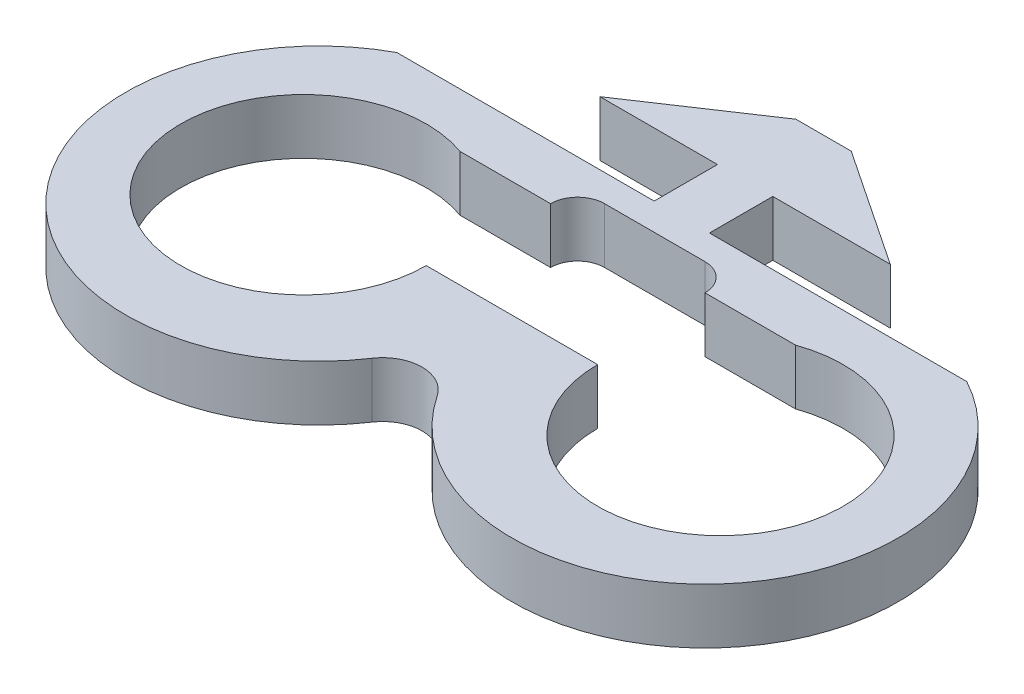
SolidWorks part; units mm, degrees
ref_plane "Front" through (0, 0, 0) normal (0, 0, 1) x (1, 0, 0)
ref_plane "Top" through (0, 0, 0) normal (0, 1, 0) x (1, 0, 0)
ref_plane "Right" through (0, 0, 0) normal (1, 0, 0) x (0, 0, -1)
sketch "Sketch1" plane through (0, 0, 0) normal (0, 1, 0) x (1, 0, 0)
  line L0 (-1.7907, 2.05) -> (-9.398, 2.05)
  line L2 (-1.7907, -2.05) -> (-1.7907, 2.05)
  line L4 (1.7907, -2.05) -> (1.7907, 2.05)
  line L7 (-9.398, 2.05) -> (-1.7907, 7.13)
  line L8 (-1.7907, 7.13) -> (1.7907, 7.13)
  line L9 (1.7907, 7.13) -> (9.398, 2.05)
  line L10 (9.398, 2.05) -> (1.7907, 2.05)
  line L11 (1.7907, -2.05) -> (25.0063, -2.05)
  line L12 (-1.7907, -2.05) -> (-25.0063, -2.05)
  line L13 (-25.0063, -2.05) -> (-25.0063, -13.0482)
  line L14 (-25.0063, -13.0482) -> (25.0063, -13.0482)
  line L15 (25.0063, -13.0482) -> (25.0063, -2.05)
  line L16 (25.0063, -2.05) -> (1.7907, -2.05)
  point P0 (0, 0)
  point P17 (0, 7.13)
  point P19 (0, -13.0482)
  point P24 (1.7907, 0)
  dimension "D1" = 18.796
  dimension "D2" = 3.5814
  dimension "D3" = 50.0126
  dimension "D4" = 10.9982
  dimension "D5" = 5.08
  dimension "D7" = 4.1
extrude "Boss-Extrude1" add sketch "Sketch1" along normal blind 3.5814 contours L14 L15 L11 L4 L10 L9 L8 L7 L0 L2 L12 L13 region at (0, 0, 6.3134)
sketch "Sketch3" plane through (0, 3.5814, 0) normal (0, 1, 0) x (1, 0, 0)
  line L3 (-25.0063, -13.0482) -> (25.0063, -13.0482) construction
  line L16 (-25.0063, -13.0482) -> (25.0063, -13.0482)
  line L17 (25.0063, -13.0482) -> (25.0063, -2.05)
  line L18 (25.0063, -2.05) -> (1.7907, -2.05)
  line L19 (1.7907, -2.05) -> (1.7907, 2.05)
  line L20 (1.7907, 2.05) -> (9.398, 2.05)
  line L21 (9.398, 2.05) -> (1.7907, 7.13)
  line L22 (1.7907, 7.13) -> (-1.7907, 7.13)
  line L23 (-1.7907, 7.13) -> (-9.398, 2.05)
  line L24 (-9.398, 2.05) -> (-1.7907, 2.05)
  line L25 (-1.7907, 2.05) -> (-1.7907, -2.05)
  line L26 (-1.7907, -2.05) -> (-25.0063, -2.05)
  line L27 (-25.0063, -2.05) -> (-25.0063, -13.0482)
  line L28 (-25.0063, -13.0482) -> (25.0063, -13.0482)
  arc A2 (-25.0063, -13.0482) -> (-2.1111, -20.0005) centre (-12.5031, -13.0482) ccw
  arc A3 (2.1111, -20.0005) -> (25.0063, -13.0482) centre (12.5032, -13.0482) ccw
  arc A4 (2.1111, -20.0005) -> (-2.1111, -20.0005) centre (0, -21.4129) ccw
  point P14 (0, -13.0482)
  line M15 (-25.0063, -13.0482) -> (25.0063, -13.0482)
  dimension "D2" = 2.54
  dimension "D1" = 0
extrude "Boss-Extrude2" add sketch "Sketch3" against normal up to surface (3.5814 mm away) contours A2 M15 | L28 A3 region at (0, 3.5814, 18.3456) up to face at (0, 0, 0.9864)
sketch "Sketch4" plane through (0, 3.5814, 0) normal (0, 1, 0) x (1, 0, 0)
  line L0 (-1025.0063, -13.0482) -> (48974.9937, -13.0482) construction
  circle A0 centre (-13.5, -13.0482) radius 7.95
  circle A1 centre (13.5, -13.0482) radius 7.95
  point P5 (0, 0)
  point P7 (0, 0)
  dimension "D1" = 15.9
  dimension "D2" = 13.5
  dimension "D3" = 13.5
extrude "Cut-Extrude2" cut sketch "Sketch4" against normal through all
sketch "Sketch5" plane through (0, 3.5814, 0) normal (0, 1, 0) x (1, 0, 0)
  line L2 (-3.25, -5.55) -> (3.25, -5.55) construction
  line L3 (-3.25, -3.8) -> (3.25, -3.8)
  line L5 (1.7907, -2.05) -> (25.0063, -2.05) construction
  line L8 (-5, -5.55) -> (-10.8581, -5.55)
  line L9 (5, -5.55) -> (10.8581, -5.55)
  line L10 (-5.55, -13.0482) -> (5.55, -13.0482)
  circle A0 centre (-13.5, -13.0482) radius 7.95 construction
  circle A1 centre (13.5, -13.0482) radius 7.95 construction
  arc A3 (-3.25, -3.8) -> (-5, -5.55) centre (-3.25, -5.55) ccw
  arc A4 (5, -5.55) -> (3.25, -3.8) centre (3.25, -5.55) ccw
  arc A8 (10.8581, -5.55) -> (5.55, -13.0482) centre (13.5, -13.0482) ccw
  arc A9 (-5.55, -13.0482) -> (-10.8581, -5.55) centre (-13.5, -13.0482) ccw
  point P7 (0, -5.55)
  point P12 (0, -15.5882)
  point P28 (0, -10.5082)
  dimension "D3" = 2.54
  dimension "D5" = 1.75
  dimension "D10" = 2.54
extrude "Cut-Extrude4" cut sketch "Sketch5" against normal up to next contours L8 A9 L10 A8 L9 A4 L3 A3
sketch "Sketch6" plane through (0, 3.5814, 0) normal (0, 1, 0) x (1, 0, 0)
  line L0 (-18.4503, -2.05) -> (-25.0063, -2.05)
  line L1 (-25.0063, -2.05) -> (-25.0063, -13.0482)
  line L2 (-1.7907, -2.05) -> (-25.0063, -2.05) construction
  line L3 (25.0063, -13.0482) -> (25.0063, -2.05)
  line L4 (25.0063, -2.05) -> (18.4503, -2.05)
  arc A0 (-18.4503, -2.05) -> (-25.0063, -13.0482) centre (-12.5031, -13.0482) ccw
  arc A1 (-25.0063, -13.0482) -> (-2.1111, -20.0005) centre (-12.5031, -13.0482) ccw construction
  arc A2 (25.0063, -13.0482) -> (18.4503, -2.05) centre (12.5032, -13.0482) ccw
  arc A3 (2.1111, -20.0005) -> (25.0063, -13.0482) centre (12.5032, -13.0482) ccw construction
extrude "Cut-Extrude5" cut sketch "Sketch6" against normal up to next
